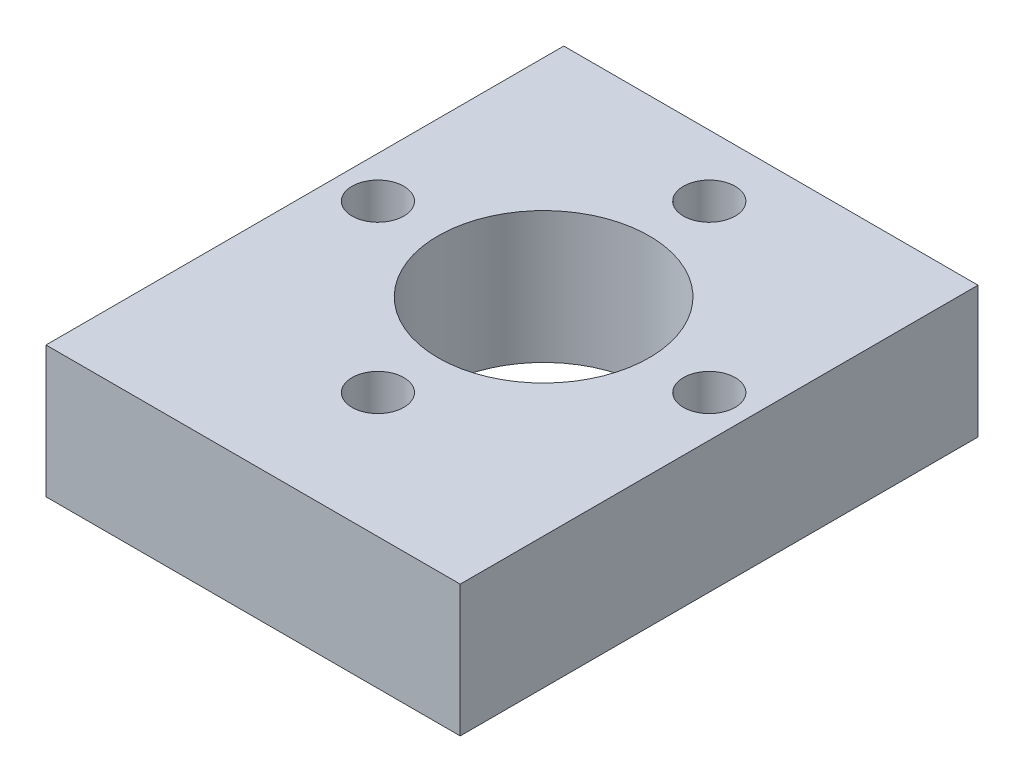
SolidWorks part; units mm, degrees
ref_plane "Front Plane" through (0, 0, 0) normal (0, 0, 1) x (1, 0, 0)
ref_plane "Top Plane" through (0, 0, 0) normal (0, 1, 0) x (1, 0, 0)
ref_plane "Right Plane" through (0, 0, 0) normal (1, 0, 0) x (0, 0, -1)
sketch "Sketch1" plane through (0, 0, 0) normal (0, 1, 0) x (1, 0, 0)
  line L1 (-10, -12.5) -> (10, -12.5)
  line L2 (-10, -12.5) -> (-10, 12.5)
  line L3 (-10, 12.5) -> (10, 12.5)
  line L4 (10, -12.5) -> (10, 12.5)
  line L5 (-10, -12.5) -> (10, 12.5) construction
  line L6 (-10, 12.5) -> (10, -12.5) construction
  circle A0 centre (0, 1.5262) radius 5.1
  point P0 (0, 1.5262)
  dimension "D1" = 10.2
  dimension "D2" = 20
  dimension "D3" = 25
  dimension "D4" = 1.5262
extrude "Boss-Extrude1" add sketch "Sketch1" along normal blind 6.35 contours L1 L4 L3 L2 A0 region at (-9.6798, 0, 0)
sketch "Sketch2" plane through (0, 6.35, 0) normal (0, 1, 0) x (1, 0, 0)
  circle A0 centre (0, 1.5262) radius 8 construction
  point P2 (0, 9.5262)
  point P4 (8, 1.5262)
  point P5 (0, -6.4738)
  point P6 (-8, 1.5262)
  dimension "D1" = 8
hole_wizard "Tap Drill for M3x0.5 Tap1" positions "Sketch2" profile "Sketch3" hole size "M3x0.5" standard "ANSI Metric" end condition through all
sketch "Sketch3" plane through (-8, 6.35, -1.5262) normal (1, 0, 0) x (0, 0, 1)
  line L0 (0, 0) -> (0, 6.35)
  line L1 (0, 6.35) -> (1.25, 6.35)
  line L2 (1.25, 6.35) -> (1.25, 0)
  line L5 (1.25, 0) -> (0, 0)
  line L11 (0, -6.35) -> (0, 107.95) construction
  dimension "Thru Hole Dia." = 2.5
  dimension "Thru Hole Depth" = 6.35
sketch "Sketch4" plane through (0, 0, -12.5) normal (0, 0, -1) x (-1, 0, 0)
  line L0 (0, 0) -> (0, 6.35) construction
  line L1 (10, 6.35) -> (-10, 6.35) construction
  line L9 (-7.62, 3.175) -> (7.62, 3.175) construction
  point P5 (0, 3.175)
  point P47 (0, 3.175)
  dimension "D1" = 15.24
hole_wizard "Tap Drill for M3x0.5 Tap3" positions "Sketch7" profile "Sketch8" hole size "M3x0.5" standard "ANSI Metric"
sketch "Sketch7" plane through (0, 0, -12.5) normal (0, 0, -1) x (-1, 0, 0)
  point P0 (-7.62, 3.175)
  point P3 (7.62, 3.175)
sketch "Sketch8" plane through (7.62, 3.175, -12.5) normal (1, 0, 0) x (0, 1, 0)
  line L0 (0, 0) -> (0, 6.7511)
  line L1 (0, 6.7511) -> (1.25, 6)
  line L2 (1.25, 6) -> (1.25, 0)
  line L5 (1.25, 0) -> (0, 0)
  line L10 (0, 6.7511) -> (-1.25, 6) construction
  line L11 (0, -6.35) -> (0, 107.95) construction
  dimension "Hole Dia." = 2.5
  dimension "Hole Depth" = 6
  dimension "Drill Angle" = 118
